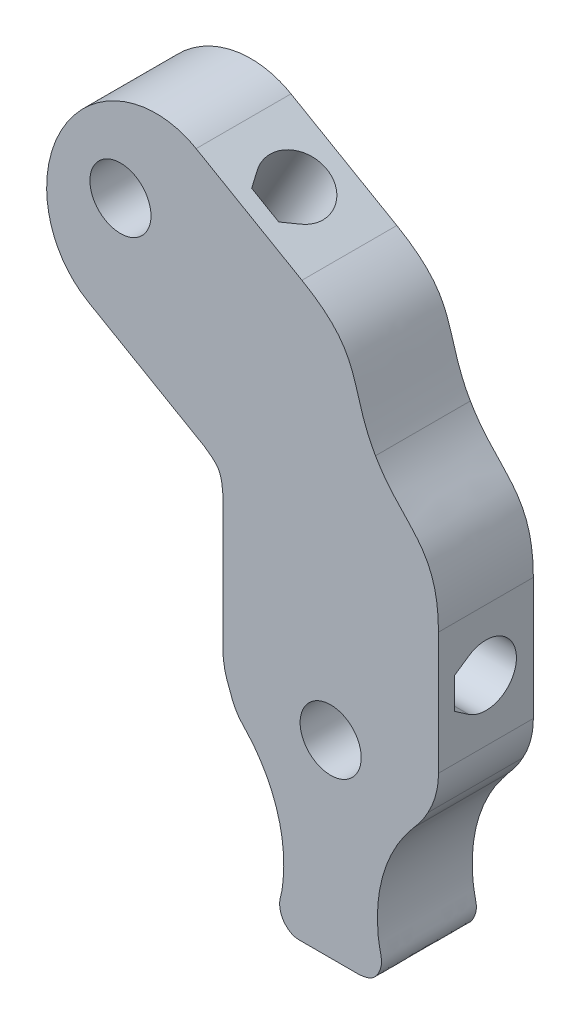
SolidWorks part; units mm, degrees
ref_plane "Piano frontale" through (0, 0, 0) normal (0, 0, 1) x (1, 0, 0)
ref_plane "Piano superiore" through (0, 0, 0) normal (0, 1, 0) x (1, 0, 0)
ref_plane "Piano destro" through (0, 0, 0) normal (1, 0, 0) x (0, 0, -1)
sketch "Schizzo1" plane through (0, 0, 0) normal (0, 0, 1) x (1, 0, 0)
  line L0 (-61.2733, -35.3762) -> (61.2733, 35.3762) construction
  line L1 (-53.5838, 0) -> (53.5838, 0) construction
  line L2 (0, 33.775) -> (0, -33.775) construction
  line L3 (-15, -13.275) -> (-15, -30.275)
  line L4 (15, -13.275) -> (15, -30.275)
  line L5 (-13.132, -13.2311) -> (-10.36, -18.0322) construction
  line L6 (15, -10.7711) -> (15, -22.7789) construction
  line L7 (3.9927, 7.4846) -> (8.4782, -0.2845) construction
  line L8 (-3.9965, 19.6279) -> (-18.7189, 28.1279)
  line L9 (-18.9965, -6.3529) -> (-33.7189, 2.1471)
  circle A0 centre (0, -33.775) radius 4.25
  circle A1 centre (-29.25, 16.8875) radius 4.25
  ellipse E0 centre (0, -30.275) end of major axis (15, -30.275) minor radius 12.681 (-15, -30.275) -> (15, -30.275) ccw
  ellipse E1 centre (-26.2189, 15.1375) end of major axis (-18.7189, 28.1279) minor radius 12.681 (-33.7189, 2.1471) -> (-18.7189, 28.1279) cw
  spline S0 degree 3 poles (-15, -13.275) (-14.8913, -10.9158) (-15.2403, -9.5793) (-15.5782, -8.9941) knots 0 0 0 0 1 1 1 1
  spline S1 degree 3 poles (15, -13.275) (15, -3.028) (10.1064, -3.1045) (6.2355, 3.6001) knots 0 0 0 0 1 1 1 1
  spline S2 degree 3 poles (-3.9965, 19.6279) (4.8777, 14.5044) (2.3646, 10.3046) (6.2355, 3.6001) knots 0 0 0 0 1 1 1 1
  spline S3 degree 3 poles (-18.9965, -6.3529) (-16.899, -7.4384) (-15.9161, -8.4088) (-15.5782, -8.9941) knots 0 0 0 0 1 1 1 1
  point P7 (0, 0)
  point P10 (0, 0)
  point P43 (0, 0)
  dimension "D3" = 8.5
  dimension "D6" = 30
  dimension "D7" = 9.181
  dimension "D1" = 30
  dimension "D2" = 3.5
  dimension "D4" = 29.25
  dimension "D5" = 17
extrude "Estrusione-Estrusione1" add sketch "Schizzo1" along normal mid plane 13.2 contours A1 | S0 S3 L9 E1 L8 S2 S1 L4 E0 L3 | A0 region at (-29.25, 16.8875, 0)
sketch "Schizzo11" plane through (15, 0, 0) normal (1, 0, 0) x (0, 0, -1)
  line L0 (-6.6, -13.275) -> (-6.6, -30.275) construction
  line L1 (6.6, -13.275) -> (6.6, -30.275) construction
  line L2 (-6.6, -13.275) -> (-6.6, -30.275) construction
  line L3 (6.6, -13.275) -> (6.6, -30.275) construction
  line L4 (-6.6, -21.775) -> (6.6, -21.775) construction
  line L5 (-4.35, -23.95) -> (-4.35, -19.6)
  line L6 (-4.35, -19.6) -> (-2.3978, -18.266)
  line L7 (-4.35, -23.95) -> (-2.3978, -25.284)
  arc A0 (-2.3978, -25.284) -> (-2.3978, -18.266) centre (0, -21.775) ccw
  point P11 (-4.35, -21.775)
  dimension "D1" = 8.5
  dimension "D2" = 2.25
  dimension "D3" = 4.35
sketch "Schizzo12" plane through (7.5, 12.9904, 0) normal (0.5, 0.866, 0) x (0.866, -0.5, 0)
  line L0 (-13.275, -6.6) -> (-30.275, -6.6) construction
  line L1 (-13.275, 6.6) -> (-30.275, 6.6) construction
  line L2 (-13.275, -6.6) -> (-30.275, -6.6) construction
  line L3 (-13.275, 6.6) -> (-30.275, 6.6) construction
  line L4 (-21.775, -6.6) -> (-21.775, 6.6) construction
  line L5 (-19.6, -4.35) -> (-23.95, -4.35)
  line L6 (-19.6, -4.35) -> (-18.266, -2.3978)
  line L7 (-23.95, -4.35) -> (-25.284, -2.3978)
  arc A0 (-18.266, -2.3978) -> (-25.284, -2.3978) centre (-21.775, 0) ccw
  point P11 (-21.775, -4.35)
  dimension "D1" = 8.5
  dimension "D2" = 2.25
  dimension "D3" = 4.35
extrude "Taglio-Estrusione1" cut sketch "Schizzo11" against normal up to next contours A0 L6 L5 L7
extrude "Taglio-Estrusione2" cut sketch "Schizzo12" against normal up to next contours A0 L7 L5 L6
sketch "Schizzo13" plane through (0, 0, -6.6) normal (0, 0, -1) x (-1, 0, 0)
  line L0 (-15, -30.275) -> (0, -39.8677)
  line L2 (-4.0218, -60.0556) -> (4.1051, -60.0556)
  line L7 (0, -39.8677) -> (15, -30.275)
  ellipse E1 centre (0, -30.275) end of major axis (-15, -30.275) minor radius 12.681 (-15, -30.275) -> (15, -30.275) ccw construction
  spline S6 degree 2 poles (-15, -30.275) (-14.7199, -35.0921) (-11.55, -38.5506) knots 0 0 0 1 1 1
  spline S7 degree 3 poles (-11.55, -38.5506) (-11.2218, -38.9151) (-10.906, -39.4003) (-9.6931, -40.981) (-8.6673, -42.7403) (-7.6766, -45.0752) (-7.089, -46.9825) (-6.6936, -48.9401) (-6.4924, -50.9279) (-6.5046, -52.9227) (-6.6441, -54.747) (-6.9987, -56.0862) (-7.1494, -57.4155) (-6.5817, -58.9215) (-5.5699, -59.8597) (-4.0678, -60.0621) (-4.0218, -60.0556) knots 0.416114 0.416114 0.416114 0.416114 0.453647 0.468506 0.553584 0.600938 0.648267 0.695593 0.742926 0.790263 0.837596 0.872691 0.888629 0.932637 0.976655 1 1 1 1
  spline S8 degree 3 poles (4.1051, -60.0556) (4.4597, -60.0586) (5.3097, -60.0368) (6.7109, -58.988) (7.1479, -57.5205) (7.0724, -56.5129) (6.77, -55.5054) (6.6064, -54.016) (6.4866, -52.0263) (6.5907, -50.0303) (6.8882, -48.056) (7.3815, -46.1204) (8.063, -44.2435) (8.9296, -42.4434) (9.9774, -40.7456) (11.0141, -39.322) (11.9647, -38.3696) (12.4063, -37.8533) (12.5655, -37.6555) knots 0 0 0 0 0.02766 0.083337 0.139001 0.15916 0.17363 0.233517 0.293375 0.353234 0.41312 0.472985 0.532856 0.592728 0.652579 0.712466 0.750775 0.77363 0.77363 0.77363 0.77363
  spline S10 degree 2 poles (15, -30.275) (14.2866, -35.6427) (12.5655, -37.6555) knots 0 0 0 1 1 1
extrude "Estrusione-Estrusione2" add sketch "Schizzo13" against normal up to surface (13.2 mm away) contours S8 S10 L7 L0 S6 S7 L2 up to face at (-9.7909, -5.6528, 6.6)
